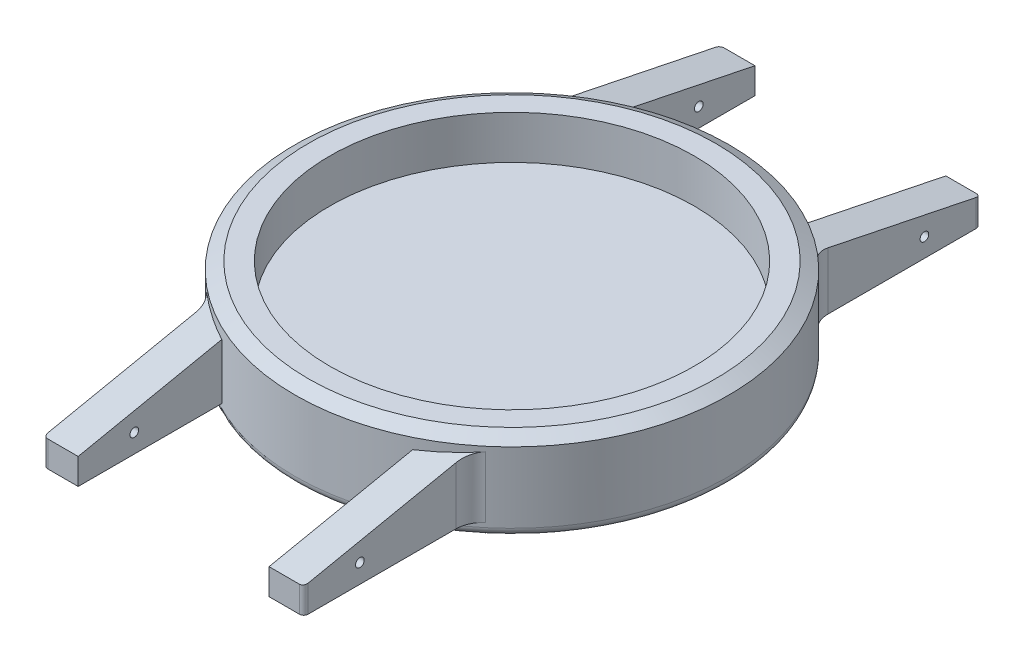
SolidWorks part; units mm, degrees
ref_plane "Front Plane" through (0, 0, 0) normal (0, 0, 1) x (1, 0, 0)
ref_plane "Top Plane" through (0, 0, 0) normal (0, 1, 0) x (1, 0, 0)
ref_plane "Right Plane" through (0, 0, 0) normal (1, 0, 0) x (0, 0, -1)
sketch "Sketch1" plane through (0, 0, 0) normal (0, 1, 0) x (1, 0, 0)
  circle A0 centre (0, 0) radius 50
extrude "Boss-Extrude1" add sketch "Sketch1" against normal blind 20
sketch "Sketch3" plane through (0, 0, 0) normal (1, 0, 0) x (0, 0, -1)
  line L0 (0, 0) -> (0, -28.4739) construction
  line L2 (34.9807, -17) -> (34.9807, -2.1601)
  line L4 (-78, -11) -> (-34.9807, -2.1601)
  line L5 (-78, -17) -> (-78, -11)
  line L6 (-78, -17) -> (-34.9807, -17)
  line L7 (78, -17) -> (34.9807, -17)
  line L9 (-50, 0) -> (-50, -20) construction
  line L10 (-34.9807, -17) -> (-34.9807, -2.1601)
  line L11 (78, -17) -> (78, -11)
  line L12 (78, -11) -> (34.9807, -2.1601)
  line L13 (-50, -20) -> (50, -20) construction
  dimension "D1" = 3
  dimension "D2" = 6
  dimension "D3" = 28
extrude "Boss-Extrude2" add sketch "Sketch3" along normal blind 30 and the other way blind 30
sketch "Sketch4" plane through (0, 0, 0) normal (0, 1, 0) x (1, 0, 0)
  line L0 (0, 0) -> (0, 78) construction
  line L1 (-30, 78) -> (30, 78) construction
  line L2 (22, 78) -> (-22, 78)
  line L3 (-22, 78) -> (-22, 44.8999)
  line L4 (-30.4715, 0) -> (29.1505, 0) construction
  line L5 (22, 78) -> (22, 44.8999)
  line L6 (-22, -78) -> (-22, -44.8999)
  line L7 (22, -78) -> (-22, -78)
  line L8 (22, -78) -> (22, -44.8999)
  arc A0 (-22, -44.8999) -> (22, -44.8999) centre (0, 0) ccw
  arc A1 (22, 44.8999) -> (-22, 44.8999) centre (0, 0) ccw
  dimension "D1" = 22
extrude "Cut-Extrude2" cut sketch "Sketch4" against normal blind 30
chamfer "Chamfer1" distance 1.75 angle 60 1 edges at (0, 0, 50) first distance on face at (-26.0576, -10.3571, -42.544)
sketch "Sketch5" plane through (0, 0, 0) normal (0, 1, 0) x (1, 0, 0)
  circle A0 centre (0, 0) radius 42
extrude "Cut-Extrude3" cut sketch "Sketch5" against normal blind 10
fillet "Fillet1" radius 6 1 edges at (30, -10.0958, 40)
fillet "Fillet2" radius 6 3 edges at (30, -10.0958, -40) (-30, -10.0958, -40) (-30, -10.0958, 40)
fillet "Fillet3" radius 2 1 edges at (0, -20, 50)
fillet "Fillet4" radius 1 4 edges at (30, -14, 78) (-30, -14, 78) (30, -14, -78) (-30, -14, -78)
sketch "Sketch7" plane through (30, 0, 0) normal (1, 0, 0) x (0, 0, -1)
  line L0 (-77, -13.8973) -> (-42.8952, -10.3932) construction
  line L1 (-77, -10.7945) -> (-77, -17) construction
  line L2 (-42.8952, -17) -> (-42.8952, -3.7864) construction
  circle A0 centre (-65.0628, -12.6708) radius 1
  dimension "D1" = 12
extrude "Cut-Extrude5" cut sketch "Sketch7" against normal blind 85 and the other way blind 20
sketch "Sketch8" plane through (30, 0, 0) normal (1, 0, 0) x (0, 0, -1)
  line L0 (42.8952, -10.3932) -> (77, -13.8973) construction
  line L1 (42.8952, -3.7864) -> (42.8952, -17) construction
  line L2 (77, -17) -> (77, -10.7945) construction
  circle A0 centre (65.0628, -12.6708) radius 1
  dimension "D1" = 12
extrude "Cut-Extrude6" cut sketch "Sketch8" against normal blind 93 and the other way blind 25
